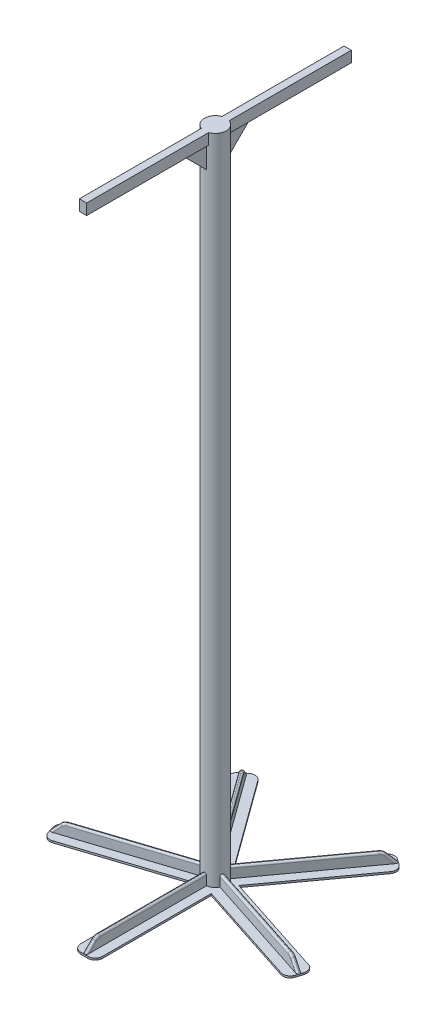
SolidWorks part; units mm, degrees
ref_plane "Front Plane" through (0, 0, 0) normal (0, 0, 1) x (1, 0, 0)
ref_plane "Top Plane" through (0, 0, 0) normal (0, 1, 0) x (1, 0, 0)
ref_plane "Right Plane" through (0, 0, 0) normal (1, 0, 0) x (0, 0, -1)
sketch "Sketch1" plane through (0, 0, 0) normal (0, 1, 0) x (1, 0, 0)
  circle A0 centre (0, 0) radius 152.4
  dimension "D1" = 304.8
extrude "Boss-Extrude1" add sketch "Sketch1" along normal blind 9144
sketch "Sketch2" plane through (0, 0, 0) normal (0, 0, 1) x (1, 0, 0)
  line L0 (-152.4, 0) -> (-152.4, 25.4)
  line L1 (-152.4, 9144) -> (-152.4, 0) construction
  line L2 (-152.4, 25.4) -> (-25.4, 25.4)
  line L3 (-25.4, 25.4) -> (-25.4, 177.8)
  line L4 (-25.4, 177.8) -> (25.4, 177.8)
  line L5 (25.4, 177.8) -> (25.4, 25.4)
  line L6 (25.4, 25.4) -> (152.4, 25.4)
  line L7 (152.4, 0) -> (152.4, 9144) construction
  line L8 (152.4, 25.4) -> (152.4, 0)
  line L9 (152.4, 0) -> (-152.4, 0)
  line L10 (-152.4, 0) -> (152.4, 0) construction
  point P5 (0, 0)
  dimension "D1" = 25.4
  dimension "D2" = 152.4
  dimension "D3" = 127
  dimension "D4" = 127
extrude "Boss-Extrude3" add sketch "Sketch2" along normal blind 1828.8
sketch "Sketch3" plane through (25.4, 0, 0) normal (1, 0, 0) x (0, 0, -1)
  line L0 (-1828.8, 25.4) -> (-1676.4, 177.8)
  line L1 (-1828.8, 177.8) -> (-150.2684, 177.8) construction
  line L2 (-1828.8, 177.8) -> (-1676.4, 177.8)
  line L3 (-1828.8, 177.8) -> (-1828.8, 25.4)
  dimension "D1" = 45
extrude "Cut-Extrude1" cut sketch "Sketch3" against normal through all
fillet "Fillet10" radius 101.6 3 edges at (-152.4, 12.7, 1828.8) (152.4, 12.7, 1828.8) (0, 177.8, 1676.4)
fillet "Fillet12" radius 25.4 6 edges at (-25.4, 86.721, 1767.479) (-25.4, 170.0662, 1673.1965) (25.4, 86.721, 1767.479) (25.4, 170.0662, 1673.1965) (-25.4, 177.8, 892.2922) (25.4, 177.8, 892.2922)
pattern_circular "CirPattern10" count 5 over 360 about axis through (0, 0, 0) along (0, 1, 0) of bodies 104
sketch "Sketch4" plane through (0, 0, 0) normal (0, 0, 1) x (1, 0, 0)
  line L0 (-50.8, 9144) -> (50.8, 9144)
  line L1 (152.4, 9144) -> (-152.4, 9144) construction
  line L2 (152.4, 9144) -> (-152.4, 9144) construction
  line L3 (50.8, 9144) -> (50.8, 8991.6)
  line L4 (50.8, 8991.6) -> (-50.8, 8991.6)
  line L5 (-50.8, 8991.6) -> (-50.8, 9144)
  line L6 (152.4, 25.4) -> (152.4, 9144) construction
  dimension "D1" = 101.6
  dimension "D2" = 101.6
  dimension "D3" = 152.4
extrude "Boss-Extrude5" add sketch "Sketch4" along normal mid plane 3695.7
sketch "Sketch5" plane through (0, 0, 0) normal (1, 0, 0) x (0, 0, -1)
  line L0 (0, 9144) -> (0, 8534.4)
  line L1 (143.6841, 9144) -> (-143.6841, 9144) construction
  line L2 (0, 8534.4) -> (-609.6, 9144)
  line L3 (-1847.85, 9144) -> (-143.6841, 9144) construction
  line L4 (-609.6, 9144) -> (0, 9144)
  dimension "D1" = 609.6
  dimension "D2" = 609.6
extrude "Boss-Extrude6" add sketch "Sketch5" along normal mid plane 50.8
pattern_circular "CirPattern11" count 2 every 180 about axis through (0, 9144, 0) along (0, 1, 0) of "Boss-Extrude6"
